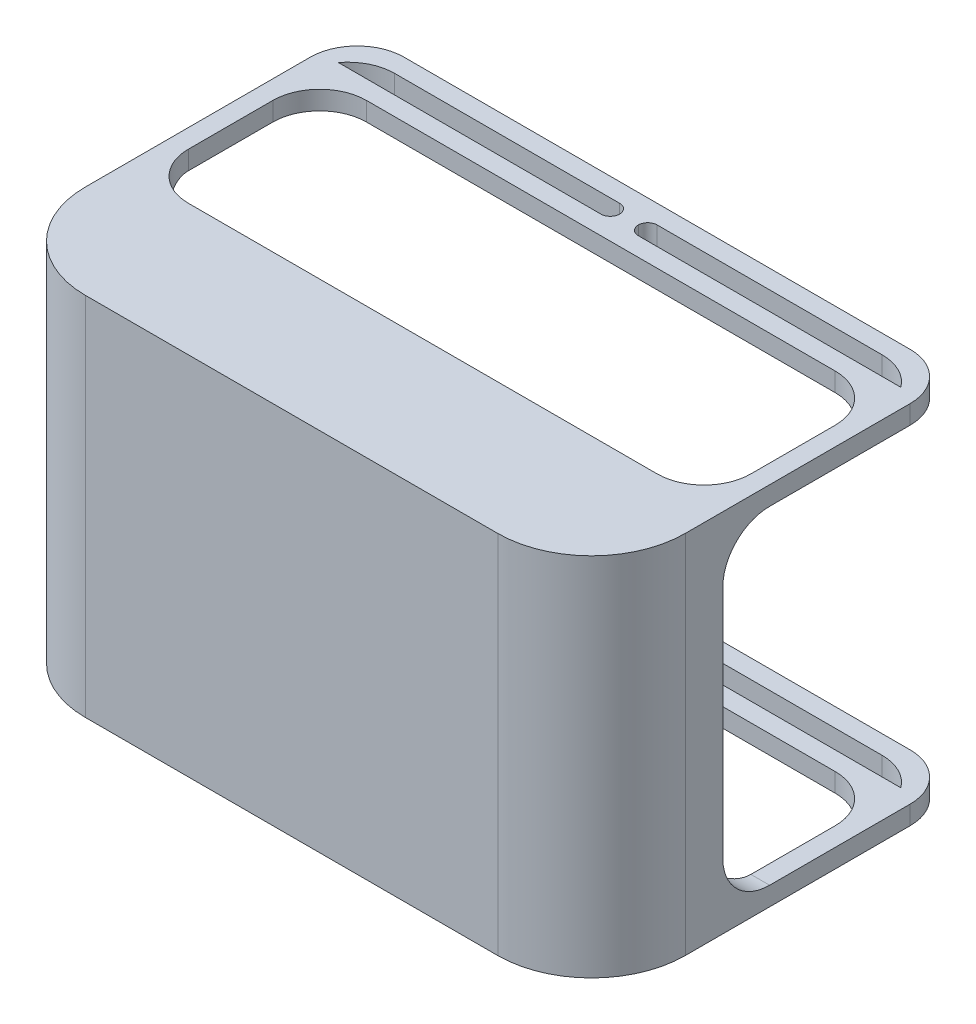
SolidWorks part; units mm, degrees
ref_plane "Front Plane" through (0, 0, 0) normal (0, 0, 1) x (1, 0, 0)
ref_plane "Top Plane" through (0, 0, 0) normal (0, 1, 0) x (1, 0, 0)
ref_plane "Right Plane" through (0, 0, 0) normal (1, 0, 0) x (0, 0, -1)
sketch "Sketch1" plane through (0, 0, 0) normal (0, 0, 1) x (1, 0, 0)
  line L0 (0, 539.4975) -> (0, -600.603) construction
  line L1 (-680.201, 0) -> (832.9648, 0) construction
  line L3 (-320, 195) -> (320, 195)
  line L4 (-320, 195) -> (-320, -195)
  line L5 (-320, -195) -> (320, -195)
  line L6 (320, 195) -> (320, -195)
  dimension "D1" = 640
  dimension "D2" = 390
extrude "Boss-Extrude1" add sketch "Sketch1" along normal blind 195 and the other way blind 195 from offset 20000 offset against normal yes
sketch "Sketch2" plane through (320, 0, 0) normal (1, 0, 0) x (0, 0, -1)
  line L0 (-6612.3529, 0) -> (64059.4281, 0) construction
  line L1 (20195, -195) -> (19805, -195) construction
  line L2 (20245, 175) -> (19945, 175)
  line L3 (20245, 175) -> (20245, -175)
  line L4 (20245, -175) -> (19945, -175)
  line L5 (19945, 175) -> (19945, -175)
  line L7 (19805, -195) -> (19805, 195) construction
  dimension "D1" = 20
  dimension "D2" = 300
  dimension "D3" = 140
extrude "Cut-Extrude1" cut sketch "Sketch2" against normal through all
sketch "Sketch3" plane through (0, -195, 0) normal (0, -1, 0) x (1, 0, 0)
  line L0 (0, 8151.9348) -> (0, -65276.6593) construction
  line L1 (-320, -20195) -> (-320, -19805) construction
  line L2 (-300, -20155) -> (-10, -20155)
  line L3 (-300, -20155) -> (-300, -20175)
  line L4 (-300, -20175) -> (-10, -20175)
  line L5 (-10, -20155) -> (-10, -20175)
  line L6 (10, -20155) -> (300, -20155)
  line L7 (10, -20155) -> (10, -20175)
  line L8 (10, -20175) -> (300, -20175)
  line L9 (300, -20155) -> (300, -20175)
  line L10 (-320, -20195) -> (320, -20195) construction
  line L12 (-300, -19945) -> (300, -19945)
  line L13 (-300, -19945) -> (-300, -20135)
  line L14 (-300, -20135) -> (300, -20135)
  line L15 (300, -19945) -> (300, -20135)
  dimension "D1" = 20
  dimension "D2" = 20
  dimension "D3" = 20
  dimension "D4" = 20
  dimension "D6" = 20
  dimension "D7" = 190
  dimension "D8" = 20
extrude "Cut-Extrude2" cut sketch "Sketch3" against normal through all
fillet "Fillet1" radius 50 20 edges at (300, 185, -20135) (300, 185, -20175) (300, -185, -20135) (300, -185, -20175) (-300, 185, -20175) (-300, 185, -20135) (300, 185, -19945) (300, -185, -19945) (-300, 185, -19945) (320, 185, -20195) (320, -185, -20195) (-320, 185, -20195) (-320, -185, -20195) (-300, -185, -19945) (-300, -185, -20175) (-300, -185, -20135) (310, -175, -19945) (310, 175, -19945) (-310, 175, -19945) (-310, -175, -19945)
fillet "Fillet2" radius 10 8 edges at (-10, -185, -20175) (-10, 185, -20175) (10, -185, -20175) (10, 185, -20175) (10, 185, -20155) (10, -185, -20155) (-10, 185, -20155) (-10, -185, -20155)
fillet "Fillet4" radius 100 2 edges at (-320, 0, -19805) (320, 0, -19805)
